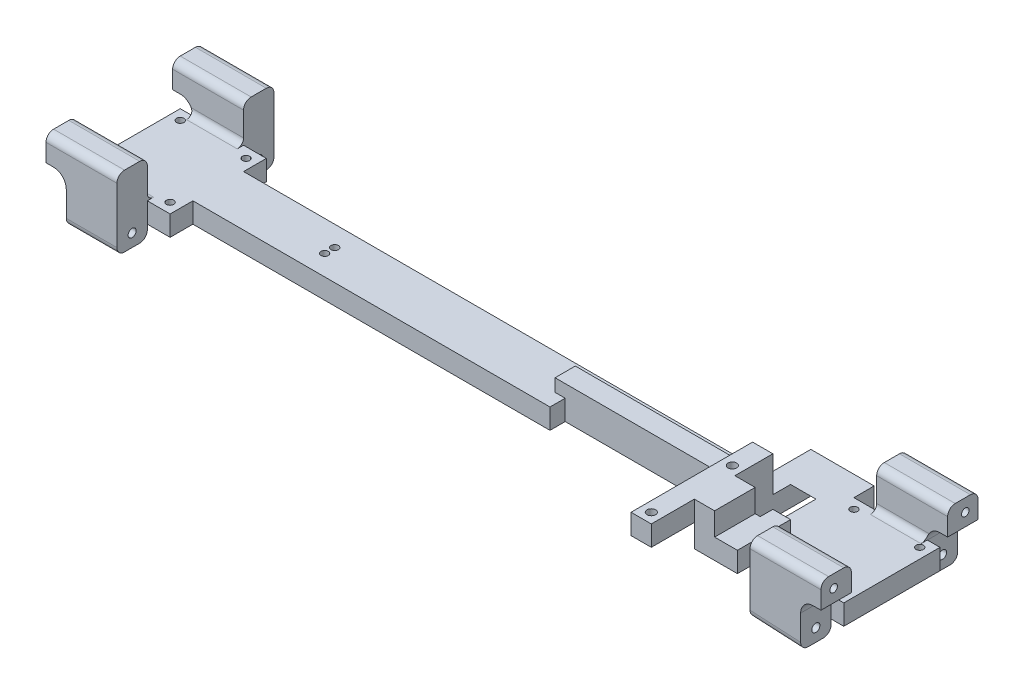
SolidWorks part; units mm, degrees
ref_plane "Front" through (0, 0, 0) normal (0, 0, 1) x (1, 0, 0)
ref_plane "Top" through (0, 0, 0) normal (0, 1, 0) x (1, 0, 0)
ref_plane "Right" through (0, 0, 0) normal (1, 0, 0) x (0, 0, -1)
sketch "Sketch1" plane through (0, 0, 0) normal (0, 1, 0) x (1, 0, 0)
  line L1 (0, 0) -> (300, 0)
  line L2 (0, 0) -> (0, -20)
  line L3 (0, -20) -> (300, -20)
  line L4 (300, 0) -> (300, -20)
  dimension "D1" = 20
  dimension "D2" = 300
extrude "Boss-Extrude1" add sketch "Sketch1" along normal blind 8
sketch "Sketch2" plane through (0, 0, 20) normal (0, 0, 1) x (1, 0, 0)
  line L0 (0, 8) -> (300, 8) construction
  line L1 (0, 0) -> (34, 0)
  line L2 (0, 0) -> (0, 8)
  line L3 (0, 8) -> (34, 8)
  line L4 (34, 0) -> (34, 8)
  line L5 (266, 8) -> (300, 8)
  line L6 (300, 0) -> (300, 8)
  line L7 (266, 0) -> (300, 0)
  line L8 (266, 0) -> (266, 8)
  dimension "D1" = 34
  dimension "D2" = 2
extrude "Boss-Extrude2" add sketch "Sketch2" along normal blind 9
sketch "Sketch3" plane through (0, 0, 0) normal (0, 0, -1) x (-1, 0, 0)
  line L0 (-300, 8) -> (0, 8) construction
  line L1 (0, 0) -> (-34, 0)
  line L2 (0, 0) -> (0, 8)
  line L3 (0, 8) -> (-34, 8)
  line L4 (-34, 0) -> (-34, 8)
  line L5 (-300, 0) -> (-300, 8)
  line L6 (-266, 8) -> (-300, 8)
  line L7 (-266, 0) -> (-266, 8)
  line L8 (-266, 0) -> (-300, 0)
  dimension "D1" = 34
  dimension "D2" = 2
extrude "Boss-Extrude3" add sketch "Sketch3" along normal blind 9
sketch "Sketch4" plane through (0, 8, 0) normal (0, 1, 0) x (1, 0, 0)
  line L0 (0, 9) -> (34, 9) construction
  line L1 (0, 9) -> (0, -29) construction
  circle A0 centre (4, 5) radius 1.45
  circle A1 centre (30, 5) radius 1.45
  circle A2 centre (30, -25) radius 1.45
  circle A3 centre (4, -25) radius 1.45
  circle A4 centre (296, -25) radius 1.45
  circle A5 centre (296, 5) radius 1.45
  circle A6 centre (270, -25) radius 1.45
  circle A7 centre (270, 5) radius 1.45
  dimension "D1" = 2.9
  dimension "D2" = 4
  dimension "D3" = 4
  dimension "D4" = 2
  dimension "D5" = 2
  dimension "D6" = 2
extrude "Cut-Extrude1" cut sketch "Sketch4" against normal through all
sketch "Sketch5" plane through (0, 0, 20) normal (0, 0, 1) x (1, 0, 0)
  line L0 (34, 8) -> (266, 8) construction
  line L1 (266, 0) -> (241, 0)
  line L2 (266, 0) -> (266, 8)
  line L3 (266, 8) -> (241, 8)
  line L4 (241, 0) -> (241, 8)
  dimension "D1" = 25
extrude "Boss-Extrude4" add sketch "Sketch5" along normal blind 17
sketch "Sketch6" plane through (0, 0, 0) normal (0, 0, -1) x (-1, 0, 0)
  line L0 (-266, 0) -> (-34, 0) construction
  line L1 (-266, 8) -> (-241, 8)
  line L2 (-266, 8) -> (-266, 0)
  line L3 (-266, 0) -> (-241, 0)
  line L4 (-241, 8) -> (-241, 0)
  dimension "D1" = 25
extrude "Boss-Extrude5" add sketch "Sketch6" along normal blind 17
sketch "Sketch12" plane through (0, 0, 37) normal (0, 0, 1) x (1, 0, 0)
  line L0 (241, 0) -> (266, 0) construction
  line L1 (241, 8) -> (249, 8)
  line L2 (241, 8) -> (241, 0)
  line L3 (241, 0) -> (249, 0)
  line L4 (249, 8) -> (249, 0)
  dimension "D1" = 8
extrude "Boss-Extrude7" add sketch "Sketch12" along normal blind 17
sketch "Sketch14" plane through (0, 0, 29) normal (0, 0, 1) x (1, 0, 0)
  line L0 (300, 8) -> (266, 8) construction
  line L1 (294.975, 8) -> (275, 8)
  line L2 (294.975, 8) -> (294.975, -5)
  line L3 (294.975, -5) -> (275, -4)
  line L4 (275, 8) -> (275, -4)
  line L7 (266, 8) -> (266, 0) construction
  dimension "D1" = 20
  dimension "D2" = 9
  dimension "D3" = 13
  dimension "D4" = 12
extrude "Boss-Extrude8" add sketch "Sketch14" along normal blind 12
sketch "Sketch15" plane through (294.975, 0, 0) normal (1, 0, 0) x (0, 0, -1)
  line L0 (-41, -5) -> (-41, 8) construction
  line L2 (-41, -5) -> (-29, -5) construction
  circle A0 centre (-35, 0) radius 1.6
  dimension "D1" = 3.2
  dimension "D2" = 6
  dimension "D3" = 5
extrude "Cut-Extrude7" cut sketch "Sketch15" against normal blind 20
sketch "Sketch16" plane through (0, 0, -9) normal (0, 0, -1) x (-1, 0, 0)
  line L0 (-266, 8) -> (-300, 8) construction
  line L1 (-295, 8) -> (-275, 8)
  line L2 (-295, 8) -> (-295, -5)
  line L3 (-295, -5) -> (-275, -5)
  line L4 (-275, 8) -> (-275, -5)
  line L6 (-266, 0) -> (-266, 8) construction
  dimension "D1" = 20
  dimension "D2" = 9
  dimension "D3" = 13
extrude "Boss-Extrude9" add sketch "Sketch16" along normal blind 12
sketch "Sketch17" plane through (295, 0, 0) normal (1, 0, 0) x (0, 0, -1)
  line L0 (21, -5) -> (9, -5) construction
  line L1 (21, 8) -> (21, -5) construction
  circle A0 centre (15, 0) radius 1.6
  dimension "D1" = 3.2
  dimension "D2" = 5
  dimension "D3" = 6
extrude "Cut-Extrude8" cut sketch "Sketch17" against normal blind 20
sketch "Sketch18" plane through (0, 0, -9) normal (0, 0, -1) x (-1, 0, 0)
  line L0 (0, 8) -> (-34, 8) construction
  line L1 (-25, 8) -> (-5, 8)
  line L2 (-25, 8) -> (-25, -5)
  line L3 (-25, -5) -> (-5, -5)
  line L4 (-5, 8) -> (-5, -5)
  line L6 (-34, 8) -> (-34, 0) construction
  dimension "D1" = 20
  dimension "D2" = 9
  dimension "D3" = 13
extrude "Boss-Extrude10" add sketch "Sketch18" along normal blind 12
sketch "Sketch19" plane through (5, 0, 0) normal (-1, 0, 0) x (0, 0, 1)
  line L0 (-21, -5) -> (-21, 8) construction
  line L2 (-21, -5) -> (-9, -5) construction
  circle A0 centre (-15, 0) radius 1.6
  dimension "D1" = 3.2
  dimension "D2" = 6
  dimension "D3" = 5
extrude "Cut-Extrude9" cut sketch "Sketch19" against normal blind 20
sketch "Sketch20" plane through (0, 0, 29) normal (0, 0, 1) x (1, 0, 0)
  line L0 (34, 8) -> (0, 8) construction
  line L1 (5, 8) -> (25, 8)
  line L2 (5, 8) -> (5, -5)
  line L3 (5, -5) -> (25, -5)
  line L4 (25, 8) -> (25, -5)
  line L6 (34, 0) -> (34, 8) construction
  dimension "D1" = 20
  dimension "D2" = 9
  dimension "D3" = 13
extrude "Boss-Extrude11" add sketch "Sketch20" along normal blind 12
sketch "Sketch21" plane through (5, 0, 0) normal (-1, 0, 0) x (0, 0, 1)
  line L0 (41, 8) -> (41, -5) construction
  line L1 (41, -5) -> (29, -5) construction
  circle A0 centre (35, 0) radius 1.6
  dimension "D1" = 3.2
  dimension "D2" = 6
  dimension "D3" = 5
extrude "Cut-Extrude10" cut sketch "Sketch21" against normal blind 20
sketch "Sketch22" plane through (0, 8, 0) normal (0, 1, 0) x (1, 0, 0)
  line L0 (241, 17) -> (241, 0) construction
  line L1 (259, 9) -> (249, 9)
  line L2 (259, 9) -> (259, -29)
  line L3 (259, -29) -> (249, -29)
  line L4 (249, 9) -> (249, -29)
  line L5 (241, 17) -> (266, 17) construction
  line L6 (266, -37) -> (249, -37) construction
  dimension "D1" = 8
  dimension "D2" = 10
  dimension "D3" = 8
  dimension "D4" = 8
extrude "Cut-Extrude11" cut sketch "Sketch22" against normal through all
sketch "Sketch23" plane through (0, 0, 0) normal (0, -1, 0) x (-1, 0, 0)
  line L0 (-259, -29) -> (-259, 9) construction
  line L1 (-259, -19) -> (-267, -19)
  line L2 (-259, -19) -> (-259, -1)
  line L3 (-259, -1) -> (-267, -1)
  line L4 (-267, -19) -> (-267, -1)
  line L5 (-249, -29) -> (-259, -29) construction
  dimension "D1" = 8
  dimension "D2" = 10
  dimension "D3" = 10
extrude "Cut-Extrude12" cut sketch "Sketch23" against normal blind 4
sketch "Sketch24" plane through (259, 0, 0) normal (-1, 0, 0) x (0, 0, 1)
  line L0 (-9, 0) -> (-9, 8)
  line L1 (-9, 8) -> (-1, 8)
  line L2 (29, 8) -> (-9, 8) construction
  line L3 (-1, 8) -> (-9, 0)
  line L4 (29, 0) -> (29, 8)
  line L5 (29, 8) -> (21, 8)
  line L6 (21, 8) -> (29, 0)
  dimension "D1" = 8
  dimension "D2" = 8
extrude "Boss-Extrude12" add sketch "Sketch24" along normal blind 10
sketch "Sketch25" plane through (267, 0, 0) normal (-1, 0, 0) x (0, 0, 1)
  line L0 (19, 0) -> (19, 4)
  line L1 (19, 4) -> (15, 4)
  line L2 (1, 4) -> (19, 4) construction
  line L3 (15, 4) -> (19, 0)
  line L4 (1, 4) -> (5, 4)
  line L5 (5, 4) -> (1, 0)
  line L6 (1, 0) -> (1, 4)
  dimension "D1" = 4
  dimension "D2" = 4
extrude "Boss-Extrude13" add sketch "Sketch25" along normal blind 8
sketch "Sketch26" plane through (0, 8, 0) normal (0, 1, 0) x (1, 0, 0)
  line L0 (249, 1) -> (249, -21) construction
  line L1 (241, -54) -> (249, -54)
  line L2 (241, -54) -> (241, -6)
  line L3 (241, -6) -> (249, -6)
  line L4 (249, -54) -> (249, -6)
  dimension "D1" = 48
extrude "Boss-Extrude14" add sketch "Sketch26" along normal blind 14
sketch "Sketch27" plane through (0, 8, 0) normal (0, 1, 0) x (1, 0, 0)
  line L0 (249, -21) -> (259, -21) construction
  line L1 (249, -37) -> (257, -37)
  line L2 (249, -37) -> (249, -21)
  line L3 (249, -21) -> (257, -21)
  line L4 (257, -37) -> (257, -21)
  dimension "D1" = 8
extrude "Boss-Extrude15" add sketch "Sketch27" along normal blind 14
sketch "Sketch28" plane through (0, 0, 0) normal (0, -1, 0) x (1, 0, 0)
  line L0 (249, -9) -> (249, 29) construction
  line L1 (241, 54) -> (249, 54)
  line L2 (241, 54) -> (241, 14)
  line L3 (241, 14) -> (249, 14)
  line L4 (249, 54) -> (249, 14)
  dimension "D1" = 40
extrude "Cut-Extrude13" cut sketch "Sketch28" against normal blind 14
sketch "Sketch30" plane through (257, 0, 0) normal (1, 0, 0) x (0, 0, -1)
  line L0 (-37, 22) -> (-21, 22) construction
  line L1 (-21, 22) -> (-37, 22)
  line L2 (-21, 22) -> (-21, 8)
  line L3 (-21, 8) -> (-37, 8)
  line L4 (-37, 22) -> (-37, 8)
extrude "Boss-Extrude16" add sketch "Sketch30" along normal blind 9
sketch "Sketch31" plane through (0, 0, 0) normal (0, -1, 0) x (-1, 0, 0)
  line L1 (-249, -37) -> (-266, -37)
  line L2 (-249, -37) -> (-249, -29)
  line L3 (-249, -29) -> (-266, -29)
  line L4 (-266, -37) -> (-266, -29)
extrude "Cut-Extrude14" cut sketch "Sketch31" against normal blind 5
sketch "Sketch32" plane through (266, 0, 0) normal (1, 0, 0) x (0, 0, -1)
  line L0 (-37, 5) -> (-37, 22) construction
  line L1 (-21, 22) -> (-37, 22)
  line L2 (-21, 22) -> (-21, 13)
  line L3 (-21, 13) -> (-37, 13)
  line L4 (-37, 22) -> (-37, 13)
  dimension "D1" = 9
extrude "Cut-Extrude15" cut sketch "Sketch32" against normal blind 9
sketch "Sketch33" plane through (249, 0, 0) normal (-1, 0, 0) x (0, 0, 1)
  line L0 (29, 5) -> (24, 5)
  line L1 (21, 8) -> (29, 0) construction
  line L2 (24, 5) -> (29, 0)
  line L3 (29, 0) -> (29, 5)
extrude "Cut-Extrude16" cut sketch "Sketch33" against normal blind 10
sketch "Sketch34" plane through (0, 0, 29) normal (0, 0, 1) x (1, 0, 0)
  line L1 (266, 5) -> (259, 5)
  line L2 (266, 5) -> (266, 0)
  line L3 (266, 0) -> (259, 0)
  line L4 (259, 5) -> (259, 0)
extrude "Cut-Extrude17" cut sketch "Sketch34" against normal blind 5
sketch "Sketch35" plane through (0, 0, 21) normal (0, 0, -1) x (-1, 0, 0)
  line L0 (-249, 8) -> (-259, 8) construction
  line L1 (-259, 8) -> (-266, 8)
  line L2 (-259, 8) -> (-259, 13)
  line L3 (-259, 13) -> (-266, 13)
  line L4 (-266, 8) -> (-266, 13)
  line L5 (-266, 8) -> (-259, 8) construction
  line L6 (-266, 8) -> (-266, 13) construction
extrude "Boss-Extrude17" add sketch "Sketch35" along normal blind 5
sketch "Sketch36" plane through (0, 22, 0) normal (0, 1, 0) x (1, 0, 0)
  line L0 (241, -54) -> (249, -54) construction
  line L1 (249, -54) -> (249, -37) construction
  circle A0 centre (245, -50) radius 1.7
  circle A1 centre (245, -18) radius 1.7
  dimension "D1" = 3.4
  dimension "D2" = 4
  dimension "D3" = 4
  dimension "D4" = 2
extrude "Cut-Extrude18" cut sketch "Sketch36" against normal through all
sketch "Sketch37" plane through (0, 8, 0) normal (0, 1, 0) x (1, 0, 0)
  line L0 (241, -6) -> (171, -6)
  line L1 (241, -6) -> (241, -14) construction
  line L2 (241, -6) -> (241, -14)
  line L3 (241, -14) -> (241, -20) construction
  line L4 (241, -14) -> (171, -14)
  line L5 (171, -14) -> (171, -6)
  dimension "D1" = 70
extrude "Boss-Extrude18" add sketch "Sketch37" along normal blind 5
sketch "Sketch39" plane through (0, 8, 0) normal (0, 1, 0) x (1, 0, 0)
  line L0 (34, -20) -> (241, -20) construction
  line L1 (241, -14) -> (175, -14)
  line L2 (241, -14) -> (241, -20)
  line L3 (241, -20) -> (175, -20)
  line L4 (175, -14) -> (175, -20)
  dimension "D1" = 66
extrude "Cut-Extrude19" cut sketch "Sketch39" against normal through all
sketch "Sketch40" plane through (0, 8, 0) normal (0, 1, 0) x (1, 0, 0)
  line L1 (5, 9) -> (25, 9)
  line L2 (5, 9) -> (5, 21)
  line L3 (5, 21) -> (25, 21)
  line L4 (25, 9) -> (25, 21)
extrude "Boss-Extrude19" add sketch "Sketch40" along normal blind 10
sketch "Sketch41" plane through (0, 18, 0) normal (0, 1, 0) x (1, 0, 0)
  line L0 (25, 21) -> (5, 21) construction
  line L1 (25, 21) -> (-3, 21)
  line L2 (25, 21) -> (25, 9)
  line L3 (25, 9) -> (-3, 9)
  line L4 (-3, 21) -> (-3, 9)
  line L5 (5, 9) -> (25, 9) construction
  line L6 (25, 9) -> (25, 21) construction
  line L7 (5, 21) -> (5, 9) construction
  dimension "D1" = 28
  dimension "D2" = 20
extrude "Boss-Extrude20" add sketch "Sketch41" along normal blind 5 and the other way blind 5
sketch "Sketch42" plane through (-3, 0, 0) normal (-1, 0, 0) x (0, 0, 1)
  line L0 (-21, 23) -> (-9, 23) construction
  line L1 (-9, 13) -> (-9, 23) construction
  circle A0 centre (-14, 18) radius 1.5
  dimension "D1" = 3
  dimension "D2" = 5
  dimension "D3" = 5
extrude "Cut-Extrude20" cut sketch "Sketch42" against normal blind 15
sketch "Sketch43" plane through (0, 8, 0) normal (0, 1, 0) x (1, 0, 0)
  line L1 (5, -41) -> (25, -41)
  line L2 (5, -41) -> (5, -29)
  line L3 (5, -29) -> (25, -29)
  line L4 (25, -41) -> (25, -29)
extrude "Boss-Extrude21" add sketch "Sketch43" along normal blind 10
sketch "Sketch44" plane through (0, 18, 0) normal (0, 1, 0) x (1, 0, 0)
  line L0 (25, -29) -> (5, -29) construction
  line L1 (-3, -29) -> (25, -29)
  line L2 (-3, -29) -> (-3, -41)
  line L3 (-3, -41) -> (25, -41)
  line L4 (25, -29) -> (25, -41)
  line L5 (5, -41) -> (25, -41) construction
  line L6 (25, -41) -> (25, -29) construction
  line L7 (5, -29) -> (5, -41) construction
  dimension "D1" = 28
  dimension "D2" = 20
extrude "Boss-Extrude22" add sketch "Sketch44" along normal blind 5 and the other way blind 5
sketch "Sketch45" plane through (-3, 0, 0) normal (-1, 0, 0) x (0, 0, 1)
  line L0 (29, 23) -> (41, 23) construction
  line L1 (41, 13) -> (41, 23) construction
  circle A0 centre (36, 18) radius 1.5
  dimension "D1" = 3
  dimension "D2" = 5
  dimension "D3" = 5
extrude "Cut-Extrude21" cut sketch "Sketch45" against normal blind 15
sketch "Sketch46" plane through (0, 8, 0) normal (0, 1, 0) x (1, 0, 0)
  line L1 (295, 9) -> (275, 9)
  line L2 (295, 9) -> (295, 21)
  line L3 (295, 21) -> (275, 21)
  line L4 (275, 9) -> (275, 21)
  line L5 (294.975, -41) -> (275, -41)
  line L6 (294.975, -41) -> (294.975, -29)
  line L7 (294.975, -29) -> (275, -29)
  line L8 (275, -41) -> (275, -29)
extrude "Boss-Extrude23" add sketch "Sketch46" along normal blind 10
sketch "Sketch47" plane through (0, 18, 0) normal (0, 1, 0) x (1, 0, 0)
  line L0 (295, 21) -> (275, 21) construction
  line L1 (275, 21) -> (303, 21)
  line L2 (275, 21) -> (275, 9)
  line L3 (275, 9) -> (303, 9)
  line L4 (303, 21) -> (303, 9)
  line L5 (275, 9) -> (295, 9) construction
  line L6 (294.975, -29) -> (275, -29) construction
  line L7 (274.975, -29) -> (303, -29)
  line L8 (274.975, -29) -> (274.975, -41)
  line L9 (274.975, -41) -> (303, -41)
  line L10 (303, -29) -> (303, -41)
  line L11 (275, -41) -> (294.975, -41) construction
  line L12 (275, 21) -> (275, 9) construction
  line L13 (295, 9) -> (295, 21) construction
  line L14 (275, -29) -> (275, -41) construction
  line L15 (294.975, -41) -> (294.975, -29) construction
  dimension "D1" = 28
  dimension "D2" = 20
  dimension "D3" = 28
  dimension "D4" = 20
extrude "Boss-Extrude24" add sketch "Sketch47" along normal blind 5 and the other way blind 5
sketch "Sketch48" plane through (303, 0, 0) normal (1, 0, 0) x (0, 0, -1)
  line L2 (-41, 13) -> (-41, 23) construction
  line L3 (21, 13) -> (21, 23) construction
  line L4 (9, 23) -> (21, 23) construction
  line L5 (-41, 23) -> (-29, 23) construction
  circle A0 centre (16, 18) radius 1.5
  circle A1 centre (-36, 18) radius 1.5
  dimension "D1" = 3
  dimension "D2" = 3
  dimension "D3" = 5
  dimension "D4" = 5
  dimension "D5" = 5
  dimension "D6" = 5
extrude "Cut-Extrude22" cut sketch "Sketch48" against normal blind 15
fillet "Fillet1" radius 5 4 edges at (294.975, 13, 35) (295, 13, -15) (5, 13, 35) (5, 13, -15)
fillet "Fillet2" radius 2.5 4 edges at (15, 8, -9) (15, 8, 29) (284.9875, 8, 29) (285, 8, -9)
fillet "Fillet3" radius 3 8 edges at (284.9875, -4.5, 41) (284.9875, -4.5, 29) (285, -5, -21) (285, -5, -9) (15, -5, -21) (15, -5, -9) (15, -5, 29) (15, -5, 41)
fillet "Fillet4" radius 3 8 edges at (11, 23, -21) (11, 23, -9) (11, 23, 29) (11, 23, 41) (289, 23, -9) (289, 23, -21) (288.9875, 23, 41) (288.9875, 23, 29)
sketch "Sketch49" plane through (0, 8, 0) normal (0, 1, 0) x (1, 0, 0)
  line L0 (241, 0) -> (34, 0) construction
  line L1 (34, -20) -> (175, -20) construction
  line L2 (0, 9) -> (0, -29) construction
  circle A0 centre (78, -8) radius 1.45
  circle A1 centre (78, -12) radius 1.45
  dimension "D1" = 2.9
  dimension "D2" = 2.9
  dimension "D3" = 8
  dimension "D4" = 8
  dimension "D5" = 78
  dimension "D6" = 78
extrude "Cut-Extrude23" cut sketch "Sketch49" against normal through all
